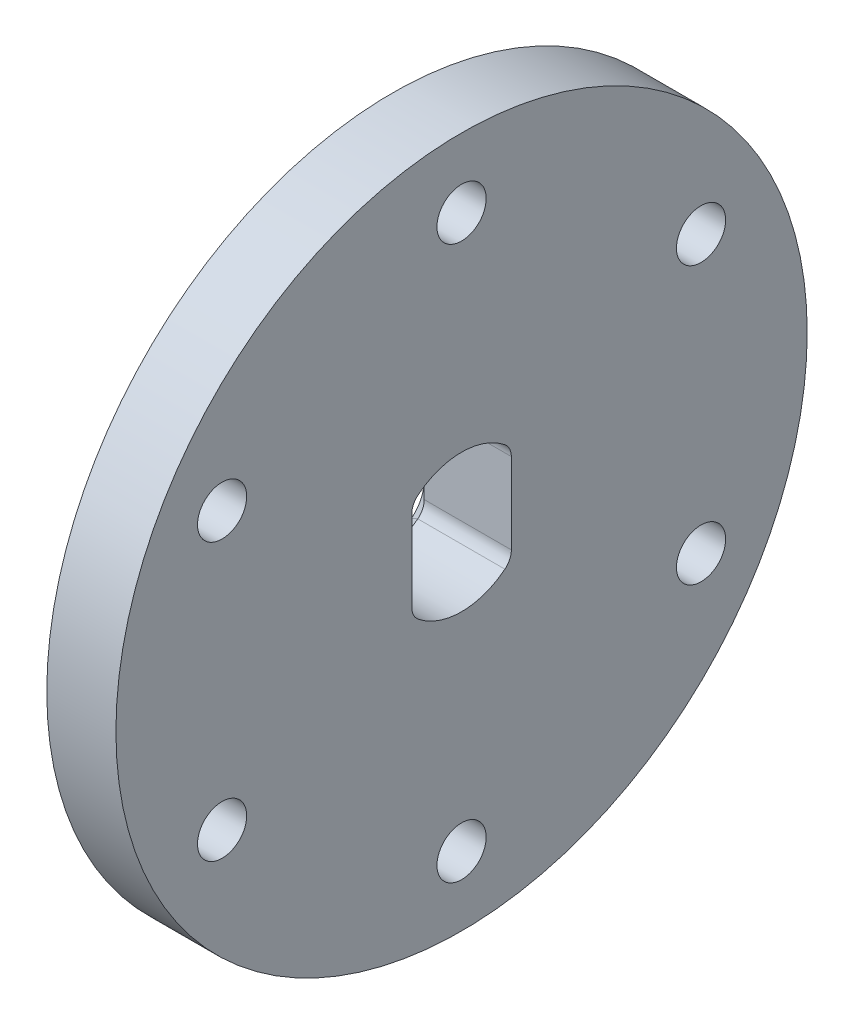
SolidWorks part; units mm, degrees
material "7075-T6 (SN)"
ref_plane "Front Plane" through (0, 0, 0) normal (0, 0, 1) x (1, 0, 0)
ref_plane "Top Plane" through (0, 0, 0) normal (0, 1, 0) x (1, 0, 0)
ref_plane "Right Plane" through (0, 0, 0) normal (1, 0, 0) x (0, 0, -1)
sketch "Sketch1" plane through (0, 0, 0) normal (1, 0, 0) x (0, 0, -1)
  circle A0 centre (0, 0) radius 15.875
  dimension "D1" = 31.75
extrude "Boss-Extrude1" add sketch "Sketch1" along normal blind 3.175
sketch "Sketch2" plane through (0, 0, 0) normal (-1, 0, 0) x (0, 0, 1)
  circle A0 centre (0, 0) radius 7.9375
  dimension "D1" = 15.875
extrude "Boss-Extrude2" add sketch "Sketch2" along normal blind 1.5875
sketch "Sketch3" plane through (3.175, 0, 0) normal (1, 0, 0) x (0, 0, -1)
  line L0 (-2.286, 2.2034) -> (-2.286, -2.2034)
  line L1 (2.286, 2.2034) -> (2.286, -2.2034)
  arc A0 (-2.286, -2.2034) -> (2.286, -2.2034) centre (0, 0) ccw
  arc A1 (2.286, 2.2034) -> (-2.286, 2.2034) centre (0, 0) ccw
  dimension "D1" = 6.35
  dimension "D2" = 2.286
  dimension "D3" = 2.286
extrude "Cut-Extrude1" cut sketch "Sketch3" against normal through all
fillet "Fillet2" radius 0.7937 4 edges at (0.7938, -2.2034, -2.286) (0.7937, -2.2034, 2.286) (0.7938, 2.2034, -2.286) (0.7938, 2.2034, 2.286)
hole_wizard "#4-40 Tapped Hole1" positions "Sketch6" profile "Sketch5" tap size "#4-40" standard "Ansi Inch"
sketch "Sketch6" plane through (3.175, 0, 0) normal (1, 0, 0) x (0, 0, -1)
  point P0 (0, 12.7)
  dimension "D1" = 12.7
sketch "Sketch5" plane through (3.175, 12.7, 0) normal (0, 1, 0) x (0, 0, -1)
  line L0 (0, 0) -> (0, 8.2992)
  line L1 (0, 8.2992) -> (1.1303, 7.62)
  line L2 (1.1303, 7.62) -> (1.1303, 0)
  line L5 (1.1303, 0) -> (0, 0)
  line L10 (0, 8.2992) -> (-1.1303, 7.62) construction
  line L11 (0, -6.35) -> (0, 107.95) construction
  dimension "Tap Drill Dia." = 2.2606
  dimension "Tap Drill Depth" = 7.62
  dimension "Drill Angle" = 118
cosmetic thread "Hole Thread1"
pattern_circular "CirPattern1" count 6 over 360 about axis through (3.175, 0, 0) along (1, 0, 0) of "#4-40 Tapped Hole1"
fillet "Fillet9" radius 1.5875 1 edges at (0, 0, -7.9375)
chamfer "Chamfer1" distance 0.762 angle 45 8 edges at (-1.5875, 0, -2.286) (-1.5875, 2.1986, -2.2081) (-1.5875, -2.1986, -2.2081) (-1.5875, 3.175, 0) (-1.5875, -3.175, 0) (-1.5875, 2.1986, 2.2081) (-1.5875, -2.1986, 2.2081) (-1.5875, 0, 2.286)
